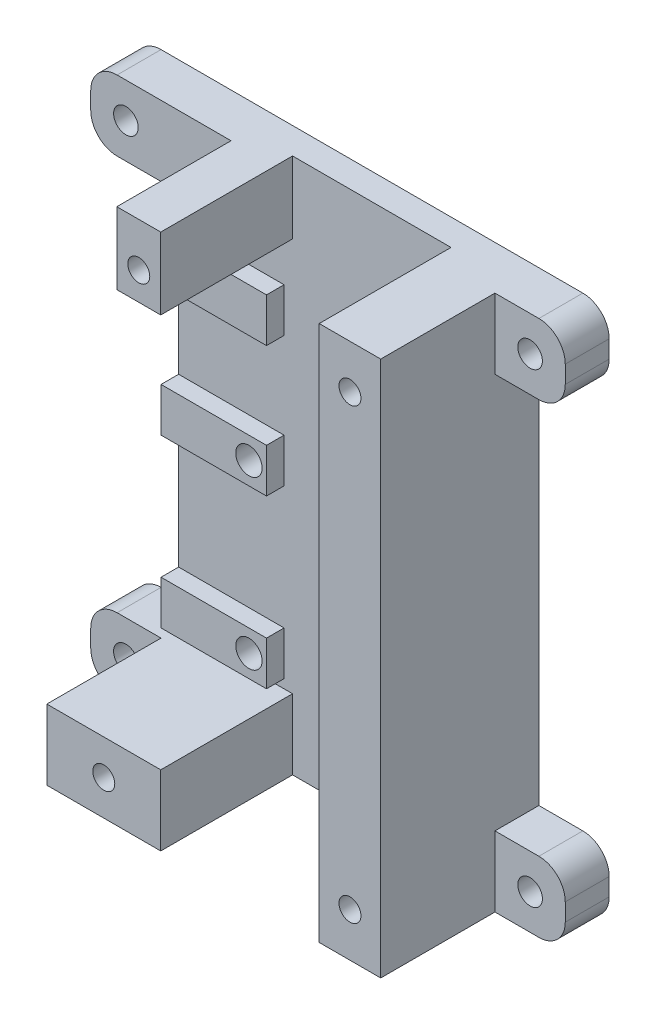
SolidWorks part; units mm, degrees
ref_plane "Plan de face" through (0, 0, 0) normal (0, 0, 1) x (1, 0, 0)
ref_plane "Plan de dessus" through (0, 0, 0) normal (0, 1, 0) x (1, 0, 0)
ref_plane "Plan de droite" through (0, 0, 0) normal (1, 0, 0) x (0, 0, -1)
sketch "Esquisse1" plane through (0, 0, 0) normal (0, 0, 1) x (1, 0, 0)
  line L1 (-17.5, -20) -> (17.5, -20)
  line L2 (-17.5, -20) -> (-17.5, 20)
  line L3 (-17.5, 20) -> (17.5, 20)
  line L4 (17.5, -20) -> (17.5, 20)
  line L5 (-17.5, -20) -> (17.5, 20) construction
  line L6 (-17.5, 20) -> (17.5, -20) construction
  point P0 (0, 0)
  dimension "D1" = 35
  dimension "D2" = 40
extrude "Boss.-Extru.1" add sketch "Esquisse1" along normal blind 3
sketch "Esquisse2" plane through (0, 0, 3) normal (0, 0, 1) x (1, 0, 0)
  line L0 (-17.5, 20) -> (-17.5, -20) construction
  line L1 (-7.5, 634.3767) -> (-7.0236, 615.3767) construction
  line L3 (-7.5, 2.5) -> (-7.5, -16.5) construction
  line L4 (-17.5, -20) -> (17.5, -20) construction
  circle A0 centre (-7.5, 634.3767) radius 2.0132
  circle A1 centre (-7.0236, 615.3767) radius 2.0132
  circle A2 centre (-7.5, 2.5) radius 1.5
  circle A3 centre (-7.5, -16.5) radius 1.5
  dimension "D3" = 3
  dimension "D1" = 19
  dimension "D2" = 10
  dimension "D4" = 10
  dimension "D5" = 19
  dimension "D6" = 22.5
extrude "Enlèv. mat.-Extru.1" cut sketch "Esquisse2" against normal blind 10
sketch "Esquisse3" plane through (0, -20, 0) normal (0, -1, 0) x (1, 0, 0)
  line L1 (-17.5, 3) -> (17.5, 3)
  line L2 (-17.5, 3) -> (-17.5, 0)
  line L3 (-17.5, 0) -> (17.5, 0)
  line L4 (17.5, 3) -> (17.5, 0)
extrude "Boss.-Extru.2" add sketch "Esquisse3" along normal blind 5
sketch "Esquisse4" plane through (0, 0, 3) normal (0, 0, 1) x (1, 0, 0)
  line L0 (17.5, -25) -> (-17.5, -25) construction
  line L1 (17.5, 20) -> (13.5, 20)
  line L2 (17.5, 20) -> (17.5, -25)
  line L3 (17.5, -25) -> (13.5, -25)
  line L4 (13.5, 20) -> (13.5, -25)
  line L6 (-17.5, -25) -> (-4.5339, -25)
  line L7 (-17.5, -25) -> (-17.5, -20)
  line L8 (-17.5, -20) -> (-4.5339, -20)
  line L9 (-4.5339, -25) -> (-4.5339, -20)
  dimension "D1" = 4
  dimension "D2" = 5
extrude "Boss.-Extru.3" add sketch "Esquisse4" along normal blind 15
sketch "Esquisse5" plane through (0, 20, 0) normal (0, 1, 0) x (1, 0, 0)
  line L6 (17.5, 0) -> (-17.5, 0)
  line L7 (-17.5, 0) -> (-17.5, -3)
  line L8 (-17.5, -3) -> (13.5, -3)
  line L9 (13.5, -3) -> (13.5, -18)
  line L10 (13.5, -18) -> (17.5, -18)
  line L11 (17.5, -18) -> (17.5, 0)
  line L12 (17.5, 0) -> (-17.5, 0)
  line L13 (-17.5, 0) -> (-17.5, -3)
  line L14 (-17.5, -3) -> (13.5, -3)
  line L15 (13.5, -3) -> (13.5, -18)
  line L16 (13.5, -18) -> (17.5, -18)
  line L17 (17.5, -18) -> (17.5, 0)
  dimension "D1" = 0
extrude "Boss.-Extru.4" add sketch "Esquisse5" along normal blind 10
sketch "Esquisse6" plane through (0, 0, 3) normal (0, 0, 1) x (1, 0, 0)
  line L0 (-17.5, 19.825) -> (13.5, 19.825) construction
  line L1 (-17.5, 30) -> (-17.5, -20) construction
  line L2 (-4.475, 19.825) -> (-20.575, 19.825) construction
  line L3 (13.5, 30) -> (13.5, -25) construction
  line L4 (-17.5, 30) -> (13.5, 30) construction
  line L5 (-4.5339, 30) -> (-9.5339, 30)
  line L6 (-4.5339, 30) -> (-4.5339, 24.825)
  line L7 (-4.5339, 24.825) -> (-9.5339, 24.825)
  line L8 (-9.5339, 30) -> (-9.5339, 24.825)
  line L9 (-4.5339, -20) -> (-4.5339, 30) construction
  dimension "D1" = 5
  dimension "D2" = 5
extrude "Boss.-Extru.5" add sketch "Esquisse6" along normal up to surface (15 mm away) up to face at (15.5, 2.5, 18)
sketch "Esquisse7" plane through (17.5, 0, 0) normal (1, 0, 0) x (0, 0, -1)
  line L4 (0, -25) -> (0, 30)
  line L5 (0, 30) -> (-18, 30)
  line L6 (-18, 30) -> (-18, -25)
  line L7 (-18, -25) -> (0, -25)
  line L8 (0, -25) -> (0, 30)
  line L9 (0, 30) -> (-18, 30)
  line L10 (-18, 30) -> (-18, -25)
  line L11 (-18, -25) -> (0, -25)
  dimension "D1" = 0
extrude "Boss.-Extru.6" add sketch "Esquisse7" along normal blind 3
sketch "Esquisse8" plane through (0, -25, 0) normal (0, -1, 0) x (1, 0, 0)
  line L8 (-17.5, 18) -> (-17.5, 0)
  line L9 (-17.5, 0) -> (20.5, 0)
  line L10 (20.5, 0) -> (20.5, 18)
  line L11 (20.5, 18) -> (13.5, 18)
  line L12 (13.5, 18) -> (13.5, 3)
  line L13 (13.5, 3) -> (-4.5339, 3)
  line L14 (-4.5339, 3) -> (-4.5339, 18)
  line L15 (-4.5339, 18) -> (-17.5, 18)
  line L16 (-17.5, 18) -> (-17.5, 0)
  line L17 (-17.5, 0) -> (20.5, 0)
  line L18 (20.5, 0) -> (20.5, 18)
  line L19 (20.5, 18) -> (13.5, 18)
  line L20 (13.5, 18) -> (13.5, 3)
  line L21 (13.5, 3) -> (-4.5339, 3)
  line L22 (-4.5339, 3) -> (-4.5339, 18)
  line L23 (-4.5339, 18) -> (-17.5, 18)
  dimension "D1" = 0
extrude "Boss.-Extru.7" add sketch "Esquisse8" along normal blind 3
sketch "Esquisse9" plane through (0, 30, 0) normal (0, 1, 0) x (1, 0, 0)
  line L10 (13.5, -18) -> (20.5, -18)
  line L11 (20.5, -18) -> (20.5, 0)
  line L12 (20.5, 0) -> (-17.5, 0)
  line L13 (-17.5, 0) -> (-17.5, -3)
  line L14 (-17.5, -3) -> (-9.5339, -3)
  line L15 (-9.5339, -3) -> (-9.5339, -18)
  line L16 (-9.5339, -18) -> (-4.5339, -18)
  line L17 (-4.5339, -18) -> (-4.5339, -3)
  line L18 (-4.5339, -3) -> (13.5, -3)
  line L19 (13.5, -3) -> (13.5, -18)
  line L20 (13.5, -18) -> (20.5, -18)
  line L21 (20.5, -18) -> (20.5, 0)
  line L22 (20.5, 0) -> (-17.5, 0)
  line L23 (-17.5, 0) -> (-17.5, -3)
  line L24 (-17.5, -3) -> (-9.5339, -3)
  line L25 (-9.5339, -3) -> (-9.5339, -18)
  line L26 (-9.5339, -18) -> (-4.5339, -18)
  line L27 (-4.5339, -18) -> (-4.5339, -3)
  line L28 (-4.5339, -3) -> (13.5, -3)
  line L29 (13.5, -3) -> (13.5, -18)
  dimension "D1" = 0
extrude "Boss.-Extru.8" add sketch "Esquisse9" along normal blind 3
sketch "Esquisse10" plane through (0, 0, 18) normal (0, 0, 1) x (1, 0, 0)
  line L0 (13.5, 33) -> (20.5, 33) construction
  line L1 (20.5, -28) -> (13.5, -28) construction
  line L2 (-7.0339, 24.825) -> (-7.0339, 33) construction
  line L3 (-4.5339, -24) -> (-17.5, -24) construction
  line L4 (-4.5339, -28) -> (-4.5339, -20) construction
  line L5 (-17.5, -20) -> (-17.5, -28) construction
  line L6 (17, 33) -> (17, -28) construction
  line L7 (17, 28) -> (-7.0339, 28) construction
  line L8 (-4.5339, 24.825) -> (-9.5339, 24.825) construction
  line L9 (-9.5339, 33) -> (-4.5339, 33) construction
  circle A0 centre (17, -23) radius 1.25
  circle A1 centre (17, 28) radius 1.25
  circle A2 centre (-11.0169, -24) radius 1.25
  circle A3 centre (-7.0339, 28) radius 1.25
  dimension "D3" = 2.5
  dimension "D1" = 5
  dimension "D2" = 5
extrude "Enlèv. mat.-Extru.2" cut sketch "Esquisse10" against normal blind 6
sketch "Esquisse11" plane through (20.5, 0, 0) normal (1, 0, 0) x (0, 0, -1)
  line L0 (0, 2.5) -> (-18, 2.5) construction
  line L1 (0, -28) -> (-5, -28)
  line L2 (0, -28) -> (0, -20)
  line L3 (0, -20) -> (-5, -20)
  line L4 (-5, -28) -> (-5, -20)
  line L5 (-18, 33) -> (-18, -28) construction
  line L6 (-5, 33) -> (-5, 25)
  line L7 (0, 25) -> (-5, 25)
  line L8 (0, 33) -> (0, 25)
  line L9 (0, 33) -> (-5, 33)
  line L10 (0, -28) -> (0, 33) construction
  line L11 (-18, -28) -> (-18, 33) construction
  dimension "D1" = 8
  dimension "D2" = 5
extrude "Boss.-Extru.9" add sketch "Esquisse11" along normal blind 8
ref_plane "Plan1" through (1.5, 0, 0) normal (1, 0, 0) x (0, 0, -1)
sketch "Esquisse12" plane through (0, 0, 5) normal (0, 0, 1) x (1, 0, 0)
  line L0 (24.5, -28) -> (24.5, 33) construction
  line L1 (28.5, -28) -> (20.5, -28) construction
  line L2 (28.5, 33) -> (20.5, 33) construction
  line L3 (28.5, -24) -> (20.5, -24) construction
  line L4 (28.5, -20) -> (28.5, -28) construction
  line L5 (20.5, -20) -> (20.5, -28) construction
  line L6 (28.5, -20) -> (28.5, 25) construction
  line L7 (24.5, 2.5) -> (28.5, 2.5) construction
  circle A0 centre (24.5, -24) radius 1.4
  circle A1 centre (24.5, 29) radius 1.4
  point P14 (24.5, -24)
  point P15 (24.5, -24)
  point P20 (28.5, 2.5)
  point P21 (24.5, 2.5)
  dimension "D1" = 2.8
extrude "Enlèv. mat.-Extru.3" cut sketch "Esquisse12" against normal blind 8
mirror "Symétrie1" about plane through (1.5, 0, 0) normal (1, 0, 0) of "Boss.-Extru.9", "Enlèv. mat.-Extru.3"
sketch "Esquisse13" plane through (0, 0, 3) normal (0, 0, 1) x (1, 0, 0)
  line L1 (-17.5, 33) -> (-9.5339, 33)
  line L2 (-17.5, 33) -> (-17.5, 24.825)
  line L3 (-17.5, 24.825) -> (-9.5339, 24.825)
  line L4 (-9.5339, 33) -> (-9.5339, 24.825)
extrude "Boss.-Extru.10" add sketch "Esquisse13" along normal up to surface (2 mm away) up to face at (-20.1, 29, 5)
sketch "Esquisse14" plane through (0, 0, 3) normal (0, 0, 1) x (1, 0, 0)
  line L0 (-17.5, 24.825) -> (-17.5, -20) construction
  line L1 (-5.5, 19.825) -> (-17.5, 19.825)
  line L2 (-5.5, 19.825) -> (-5.5, 14.825)
  line L3 (-5.5, 14.825) -> (-17.5, 14.825)
  line L4 (-17.5, 19.825) -> (-17.5, 14.825)
  line L5 (-7.175, 17.325) -> (-17.5, 17.325) construction
  line L6 (-5.5, 5) -> (-17.5, 5)
  line L7 (-5.5, 5) -> (-5.5, 0)
  line L8 (-5.5, 0) -> (-17.5, 0)
  line L9 (-17.5, 5) -> (-17.5, 0)
  line L10 (-5.5, -14) -> (-17.5, -14)
  line L11 (-5.5, -14) -> (-5.5, -19)
  line L12 (-5.5, -19) -> (-17.5, -19)
  line L13 (-17.5, -14) -> (-17.5, -19)
  line L14 (-7.5, 2.5) -> (-17.5, 2.5) construction
  line L15 (-7.5, -16.5) -> (-17.5, -16.5) construction
  circle A0 centre (-7.5, 2.5) radius 1.5
  circle A1 centre (-7.5, -16.5) radius 1.5
  circle A2 centre (-7.5, -16.5) radius 1.5 construction
  circle A3 centre (-7.5, 2.5) radius 1.5 construction
  dimension "D1" = 5
  dimension "D2" = 12
extrude "Boss.-Extru.12" add sketch "Esquisse14" along normal blind 2
fillet "Congé1" radius 3 8 edges at (-25.5, 33, 2.5) (-25.5, 25, 2.5) (-25.5, -20, 2.5) (-25.5, -28, 2.5) (28.5, 33, 2.5) (28.5, 25, 2.5) (28.5, -20, 2.5) (28.5, -28, 2.5)
sketch "Esquisse15" plane through (0, 0, 0) normal (0, 0, -1) x (-1, 0, 0)
  circle A0 centre (7.5, 2.5) radius 3.5
  circle A1 centre (7.5, -16.5) radius 3.5
  circle A2 centre (7.5, 2.5) radius 1.5
  circle A3 centre (7.5, -16.5) radius 1.5
  circle A4 centre (7.5, 2.5) radius 1.5 construction
  circle A5 centre (7.5, -16.5) radius 1.5 construction
  dimension "D1" = 7
extrude "Enlèv. mat.-Extru.4" cut sketch "Esquisse15" against normal blind 2
